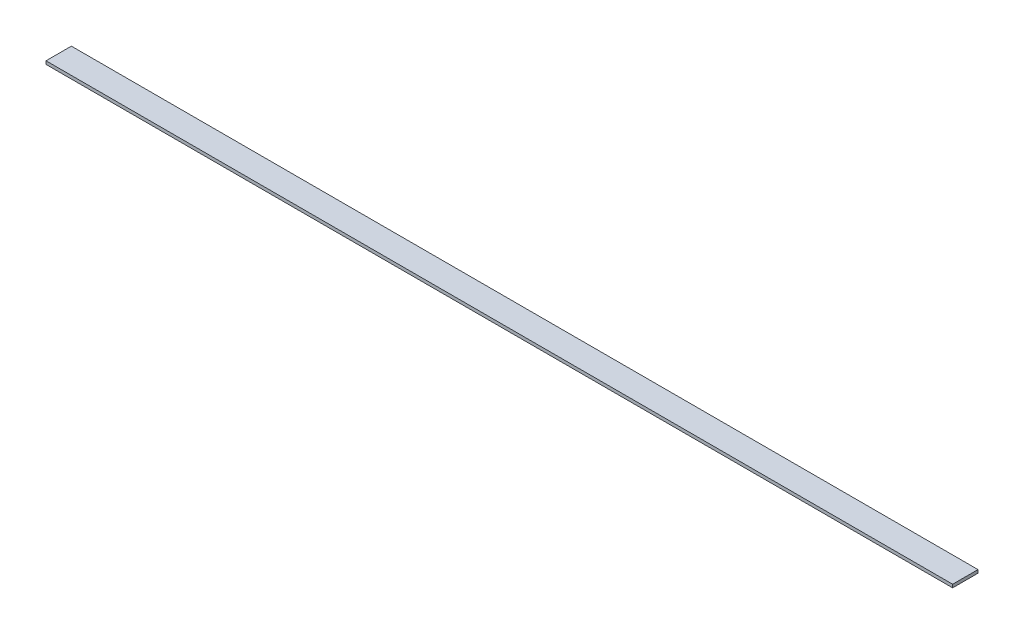
SolidWorks part; units mm, degrees
ref_plane "Front" through (0, 0, 0) normal (0, 0, 1) x (1, 0, 0)
ref_plane "Top" through (0, 0, 0) normal (0, 1, 0) x (1, 0, 0)
ref_plane "Right" through (0, 0, 0) normal (1, 0, 0) x (0, 0, -1)
sketch "Sketch2" plane through (0, 0, 0) normal (0, 1, 0) x (1, 0, 0)
  line L1 (0, 0) -> (1816.1, 0)
  line L2 (0, 0) -> (0, 50.8)
  line L3 (0, 50.8) -> (1816.1, 50.8)
  line L4 (1816.1, 0) -> (1816.1, 50.8)
  dimension "D1" = 50.8
  dimension "D2" = 1816.1
extrude "Boss-Extrude1" add sketch "Sketch2" along normal blind 6.35
